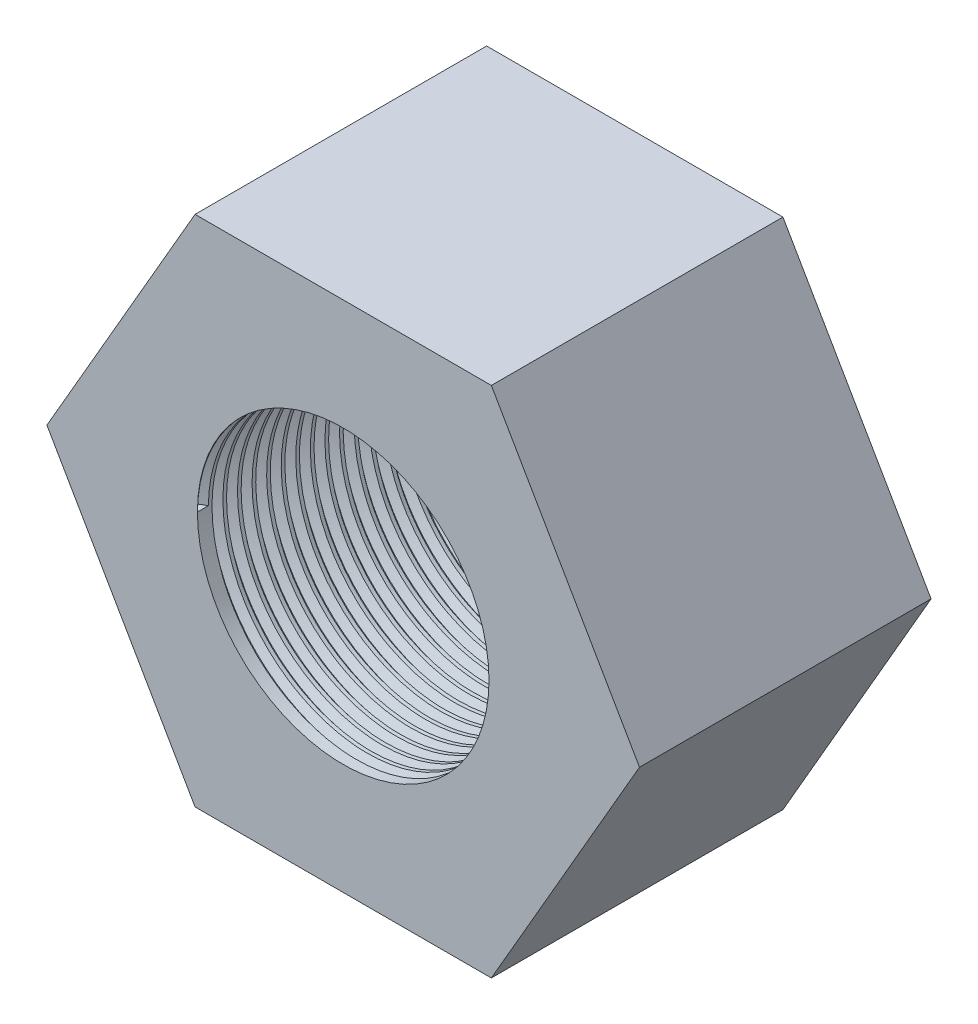
SolidWorks part; units mm, degrees
ref_plane "Front" through (0, 0, 0) normal (0, 0, 1) x (1, 0, 0)
ref_plane "Top" through (0, 0, 0) normal (0, 1, 0) x (1, 0, 0)
ref_plane "Right" through (0, 0, 0) normal (1, 0, 0) x (0, 0, -1)
sketch "Sketch1" plane through (0, 0, 0) normal (0, 0, 1) x (1, 0, 0)
  line L1 (6.4525, 0) -> (3.2262, 5.588)
  line L2 (3.2262, 5.588) -> (-3.2262, 5.588)
  line L3 (-3.2262, 5.588) -> (-6.4525, 0)
  line L4 (-6.4525, 0) -> (-3.2262, -5.588)
  line L5 (-3.2262, -5.588) -> (3.2262, -5.588)
  line L6 (3.2262, -5.588) -> (6.4525, 0)
  circle A0 centre (0, 0) radius 5.588 construction
  circle A1 centre (0, 0) radius 3.175
  dimension "D1" = 11.176
  dimension "D2" = 6.35
extrude "Boss-Extrude1" add sketch "Sketch1" along normal blind 6.35
thread "Thread1" pitch 0.3175 method cut profile "Thread Profile1" start angle 0, offset 0, length 6.35, pitch 0.3175, diameter 6.35
ref_plane "Plane1" through (-3.175, 0, 6.35) normal (0, -1, 0) x (-1, 0, 0)
sketch "Thread Profile1" plane through (-3.175, 0, 6.35) normal (0, -1, 0) x (-1, 0, 0)
  line L0 (0, 0) -> (0, 0.3175) construction
  line L1 (0, 0) -> (0.1719, 0.0992)
  line L2 (0.1719, 0.0992) -> (0.1719, 0.1389)
  line L3 (0.1719, 0.1389) -> (0, 0.2381)
  line L4 (0.1719, 0.1191) -> (0, 0.1191) construction
  line L11 (0, 0) -> (0, 0.2381)
  point P2 (0, 0)
  dimension "Pitch" = 0.3175
  dimension "Profile_Angle" = 60
  dimension "Profile_Land" = 0.0397
  dimension "Profile_Height" = 0.1719
